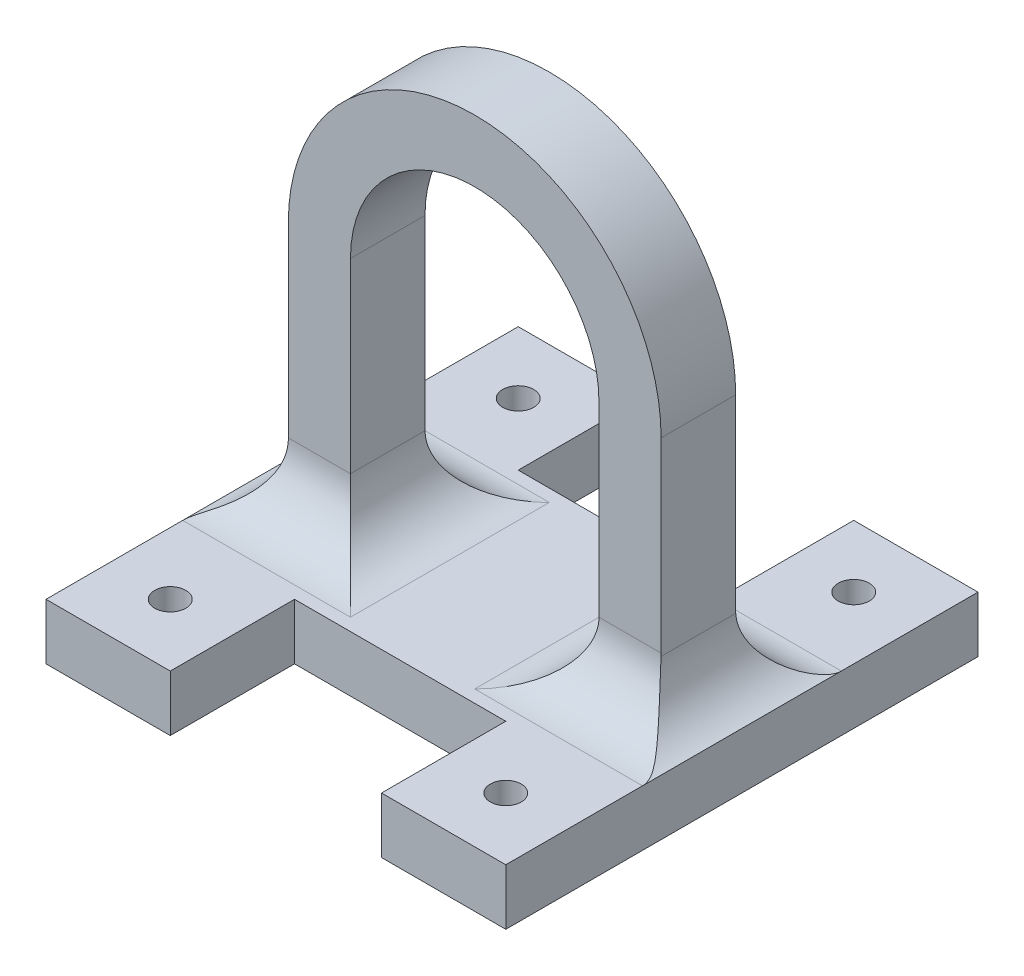
SolidWorks part; units mm, degrees
material "Onyx w/ CF"
ref_plane "Front Plane" through (0, 0, 0) normal (0, 0, 1) x (1, 0, 0)
ref_plane "Top Plane" through (0, 0, 0) normal (0, 1, 0) x (1, 0, 0)
ref_plane "Right Plane" through (0, 0, 0) normal (1, 0, 0) x (0, 0, -1)
sketch "Sketch1" plane through (0, 0, 0) normal (0, 1, 0) x (1, 0, 0)
  line L0 (18.5, 9) -> (18.5, 19)
  line L1 (-8.5, 9) -> (8.5, 9)
  line L2 (-18.5, 9) -> (-18.5, -9)
  line L3 (-8.5, -9) -> (8.5, -9)
  line L4 (18.5, 9) -> (18.5, -9)
  line L5 (-18.5, 9) -> (18.5, -9) construction
  line L6 (-18.5, -9) -> (18.5, 9) construction
  line L7 (18.5, 19) -> (8.5, 19)
  line L8 (8.5, 19) -> (8.5, 9)
  line L9 (-18.5, 9) -> (-18.5, 19)
  line L10 (-18.5, 19) -> (-8.5, 19)
  line L11 (-8.5, 19) -> (-8.5, 9)
  line L12 (-8.5, -9) -> (-8.5, -19)
  line L13 (-8.5, -19) -> (-18.5, -19)
  line L14 (-18.5, -19) -> (-18.5, -9)
  line L15 (18.5, -9) -> (18.5, -19)
  line L16 (18.5, -19) -> (8.5, -19)
  line L17 (8.5, -19) -> (8.5, -9)
  circle A0 centre (13.5, -14) radius 1.25
  circle A1 centre (13.5, 14) radius 1.25
  circle A2 centre (-13.5, 14) radius 1.25
  circle A3 centre (-13.5, -14) radius 1.25
  point P0 (0, 0)
  point P20 (18.5, 0)
  point P27 (-8.5, -14)
  point P29 (8.5, -14)
  point P31 (13.5, -19)
  point P32 (0, 9)
  point P33 (-13.5, -19)
  point P35 (-8.5, 14)
  point P36 (0, 0)
  point P40 (13.5, 19)
  point P42 (8.5, 14)
  dimension "D4" = 2.5
  dimension "D1" = 37
  dimension "D3" = 18
  dimension "D5" = 10
extrude "Boss-Extrude1" add sketch "Sketch1" along normal blind 4.5
sketch "Sketch3" plane through (0, 0, 0) normal (0, 0, 1) x (1, 0, 0)
  line L0 (-15, 4.5) -> (-15, 24.5)
  line L1 (15, 4.5) -> (15, 24.5)
  line L2 (-10, 4.5) -> (-10, 24.5)
  line L3 (-10, 4.5) -> (10, 4.5) construction
  line L4 (-10, 4.5) -> (-15, 4.5)
  line L5 (15, 4.5) -> (10, 4.5)
  line L6 (-8.5, 4.5) -> (8.5, 4.5) construction
  line L7 (10, 4.5) -> (10, 24.5)
  arc A0 (-15, 24.5) -> (15, 24.5) centre (0, 24.5) cw
  arc A1 (-10, 24.5) -> (10, 24.5) centre (0, 24.5) cw
  point P4 (0, 4.5)
  point P17 (0, 34.5)
  dimension "D1" = 5
  dimension "D2" = 30
  dimension "D3" = 20
extrude "Boss-Extrude2" add sketch "Sketch3" along normal mid plane 6
fillet "Fillet1" radius 5 8 edges at (-10, 4.5, 0) (-12.5, 4.5, -3) (-15, 4.5, 0) (-12.5, 4.5, 3) (12.5, 4.5, 3) (10, 4.5, 0) (15, 4.5, 0) (12.5, 4.5, -3)
